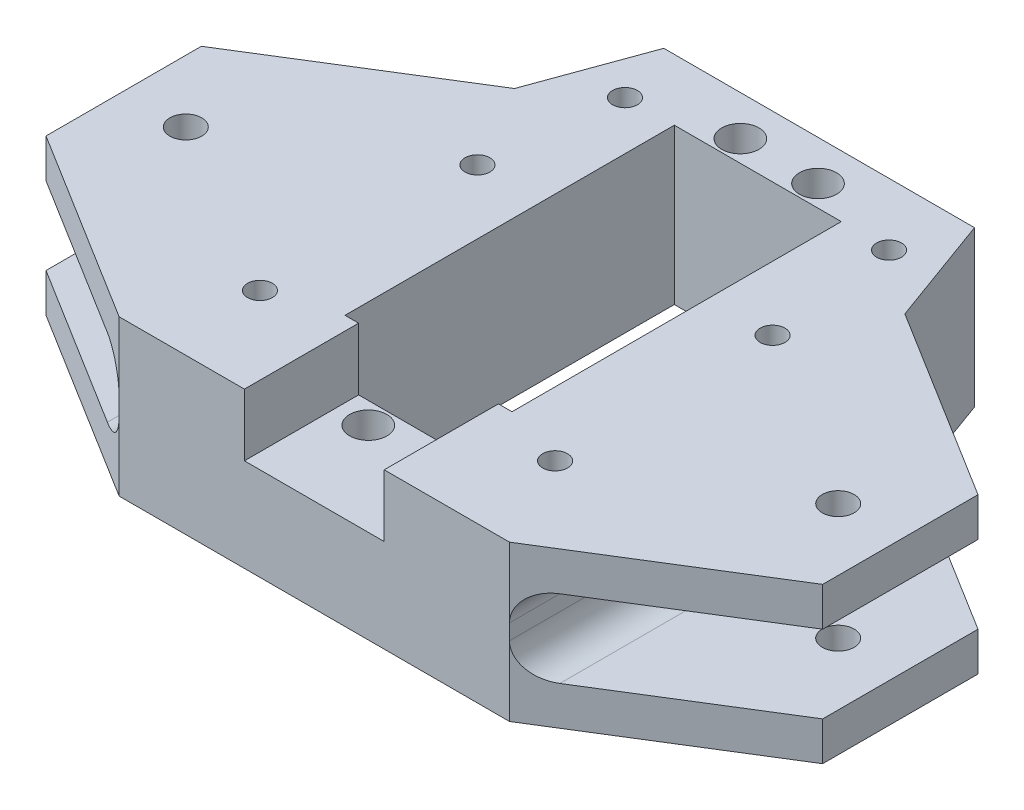
SolidWorks part; units mm, degrees
ref_plane "Front Plane" through (0, 0, 0) normal (0, 0, 1) x (1, 0, 0)
ref_plane "Top Plane" through (0, 0, 0) normal (0, 1, 0) x (1, 0, 0)
ref_plane "Right Plane" through (0, 0, 0) normal (1, 0, 0) x (0, 0, -1)
sketch "Sketch1" plane through (0, 0, 0) normal (0, 1, 0) x (1, 0, 0)
  line L0 (0, 0) -> (0, 55585.7092) construction
  line L1 (0, 0) -> (55585.7092, 0) construction
  line L2 (20, 39.5477) -> (-20, 39.5477)
  line L3 (-20, 39.5477) -> (-25.1303, 25.4523)
  line L4 (-25.1303, 25.4523) -> (-50, 10)
  line L5 (-50, 10) -> (-50, -10)
  line L11 (50, 10) -> (50, -10)
  line L12 (25.1303, 25.4523) -> (50, 10)
  line L13 (20, 39.5477) -> (25.1303, 25.4523)
  line L14 (25.1303, -25.4523) -> (50, -10)
  line L15 (-25.1303, -25.4523) -> (-50, -10)
  line L19 (25.1303, -25.4523) -> (-25.1303, -25.4523)
  point P7 (50, 0)
  point P12 (-50, 0)
  point P14 (0, -10.7407)
  point P19 (0, 39.5477)
  dimension "D1" = 40
  dimension "D2" = 20
  dimension "D3" = 65
  dimension "D4" = 100
  dimension "D5" = 110
  dimension "D8" = 15
extrude "Main-Body" add sketch "Sketch1" along normal mid plane 20
sketch "Sketch2" plane through (0, 10, 0) normal (0, 1, 0) x (1, 0, 0)
  line L0 (0, 47.5477) -> (0, -49952.4523) construction
  line L1 (-50, 0) -> (49950, 0) construction
  line L2 (20, 39.5477) -> (-20, 39.5477) construction
  line L3 (-10, 10.45) -> (10, 10.45) construction
  line L4 (10, -10) -> (-10, -10) construction
  line L5 (-10, -10) -> (-10, 30.9) construction
  line L6 (-10, 30.9) -> (10, 30.9) construction
  line L7 (10, -10) -> (10, 30.9) construction
  line L8 (0, -25.4523) -> (50000, -25.4523) construction
  line L9 (-50, 10) -> (-50, -10) construction
  line L10 (-5, 34.4) -> (5, 34.4) construction
  line L11 (-5, -13.5) -> (5, -13.5) construction
  line L12 (-25.1303, -25.4523) -> (25.1303, -25.4523) construction
  line L14 (-10.75, 31.65) -> (10.75, 31.65)
  line L15 (-10.75, 31.65) -> (-10.75, -10.75)
  line L16 (-10.75, -10.75) -> (10.75, -10.75)
  line L17 (10.75, 31.65) -> (10.75, -10.75)
  line L18 (-10.75, 31.65) -> (10.75, -10.75) construction
  line L19 (-10.75, -10.75) -> (10.75, 31.65) construction
  circle A0 centre (-5, -13.5) radius 2.4
  circle A1 centre (5, -13.5) radius 2.4
  circle A2 centre (-5, 34.4) radius 2.4
  circle A3 centre (5, 34.4) radius 2.4
  circle A4 centre (0, 0) radius 2 construction
  circle A5 centre (-42, 0) radius 2.05
  circle A6 centre (42, 0) radius 2.05
  point P22 (0, -10)
  point P23 (0, 30.9)
  point P28 (0, 39.5477)
  point P29 (0, -13.5)
  point P30 (0, 34.4)
  point P31 (-50, 0)
  point P32 (0, 10.45)
  dimension "D1" = 4.8
  dimension "D4" = 4.8
  dimension "D10" = 4.8
  dimension "D11" = 4.8
  dimension "D13" = 4
  dimension "D16" = 4.1
  dimension "D3" = 10
  dimension "D6" = 10
  dimension "D7" = 20
  dimension "D8" = 3.5
  dimension "D9" = 3.5
  dimension "D5" = 40.9
  dimension "D2" = 0.75
  dimension "D12" = 0.75
  dimension "D14" = 10
  dimension "D15" = 0
  dimension "D17" = 8
extrude "Servo&RotRod-Cutout" cut sketch "Sketch2" against normal blind 30
sketch "Sketch3" plane through (0, 0, 25.4523) normal (0, 0, 1) x (1, 0, 0)
  line L0 (0, 0) -> (0, 50000) construction
  line L1 (0, 0) -> (48695.3801, 0) construction
  line L3 (9, 10) -> (-9, 10)
  line L4 (-9, 10) -> (-9, 2)
  line L5 (-9, 2) -> (9, 2)
  line L6 (9, 10) -> (9, 2)
  line L7 (-25.1303, 10) -> (25.1303, 10) construction
  point P10 (0, 0)
  point P11 (0, 10)
  dimension "D1" = 18
  dimension "D2" = 8
  dimension "D3" = 0
extrude "Servo-Cable-Cutout" cut sketch "Sketch3" against normal up to surface (14.7023 mm away) up to face at (0, 0, 10.75)
sketch "Sketch4" plane through (0, 0, 25.4523) normal (0, 0, 1) x (1, 0, 0)
  line L0 (0, 0) -> (0, 50000) construction
  line L1 (50, 0) -> (50050, 0) construction
  line L2 (50, 10) -> (50, -10) construction
  line L3 (-50, -5) -> (-50, 5)
  line L4 (-50, 10) -> (-50, -10) construction
  line L5 (-50, 5) -> (-25.1303, 5)
  line L6 (-25.1303, 5) -> (-25.1303, -5)
  line L7 (-50, -5) -> (-25.1303, -5)
  line L10 (-25.1303, 10) -> (-25.1303, -10) construction
  point P7 (50, 0)
  point P15 (-25.1303, 0)
  point P16 (-50, 0)
  dimension "D1" = 0
  dimension "D2" = 10
extrude "Control-Arm-Cutout" cut sketch "Sketch4" against normal through all both and the other way through all
mirror "Mirror1" about plane through (0, 0, 0) normal (1, 0, 0) of "Control-Arm-Cutout"
sketch "Sketch5" plane through (0, 10, 0) normal (0, 1, 0) x (1, 0, 0)
  line L0 (-50, 0) -> (49950, 0) construction
  line L1 (-50, 10) -> (-50, -10) construction
  line L2 (0, 0) -> (0, 50000) construction
  circle A0 centre (-40, 0) radius 2.05
  point P4 (-50, 0)
  dimension "D1" = 4.1
  dimension "D2" = 10
extrude "Cut-Extrude4" [suppressed] cut sketch "Sketch5" against normal through all both and the other way through all
mirror "Mirror2" [suppressed] about plane through (0, 0, 0) normal (1, 0, 0)
fillet "Fillet1" radius 4 4 edges at (-25.1303, -5, 0) (-25.1303, 5, 0) (25.1303, -5, 0) (25.1303, 5, 0)
sketch "Sketch6" plane through (0, -10, 0) normal (0, -1, 0) x (1, 0, 0)
  line L0 (0, 0) -> (0, -50000) construction
  line L1 (19, -12.4414) -> (19, -50012.4414) construction
  line L2 (-25.1303, 25.4523) -> (25.1303, 25.4523) construction
  line L3 (20, -39.5477) -> (-20, -39.5477) construction
  circle A0 centre (19, -14.5477) radius 1.6
  circle A1 centre (19, 13.4523) radius 1.6
  circle A2 centre (17, -31.5477) radius 1.6
  circle A3 centre (-17, -31.5477) radius 1.6
  circle A4 centre (-19, 13.4523) radius 1.6
  circle A5 centre (-19, -14.5477) radius 1.6
  point P9 (0, 0)
  dimension "D2" = 3.2
  dimension "D3" = 3.2
  dimension "D7" = 3.2
  dimension "D1" = 19
  dimension "D4" = 12
  dimension "D5" = 25
  dimension "D6" = 17
  dimension "D8" = 8
extrude "Mount-Holes-Chassis" cut sketch "Sketch6" against normal through all
sketch "Sketch7" plane through (0, -10, 0) normal (0, -1, 0) x (1, 0, 0)
  line L0 (0, 0) -> (0, -50000) construction
  circle A0 centre (17, -31.5477) radius 3
  circle A1 centre (19, -14.5477) radius 3
  circle A2 centre (19, 13.4523) radius 3
  circle A3 centre (-19, 13.4523) radius 3
  circle A4 centre (-19, -14.5477) radius 3
  circle A5 centre (-17, -31.5477) radius 3
  dimension "D1" = 6
  dimension "D2" = 6
  dimension "D3" = 6
extrude "Bolt-Head-Holes" cut sketch "Sketch7" against normal blind 4
equation "\"D10@Sketch2\"=\"D1@Sketch2\""
equation "\"D11@Sketch2\"=\"D1@Sketch2\""
equation "\"D3@Sketch6\"=\"D2@Sketch6\""
equation "\"D7@Sketch6\"=\"D2@Sketch6\""
equation "\"D2@Sketch7\"=\"D1@Sketch7\""
equation "\"D3@Sketch7\"=\"D1@Sketch7\""
